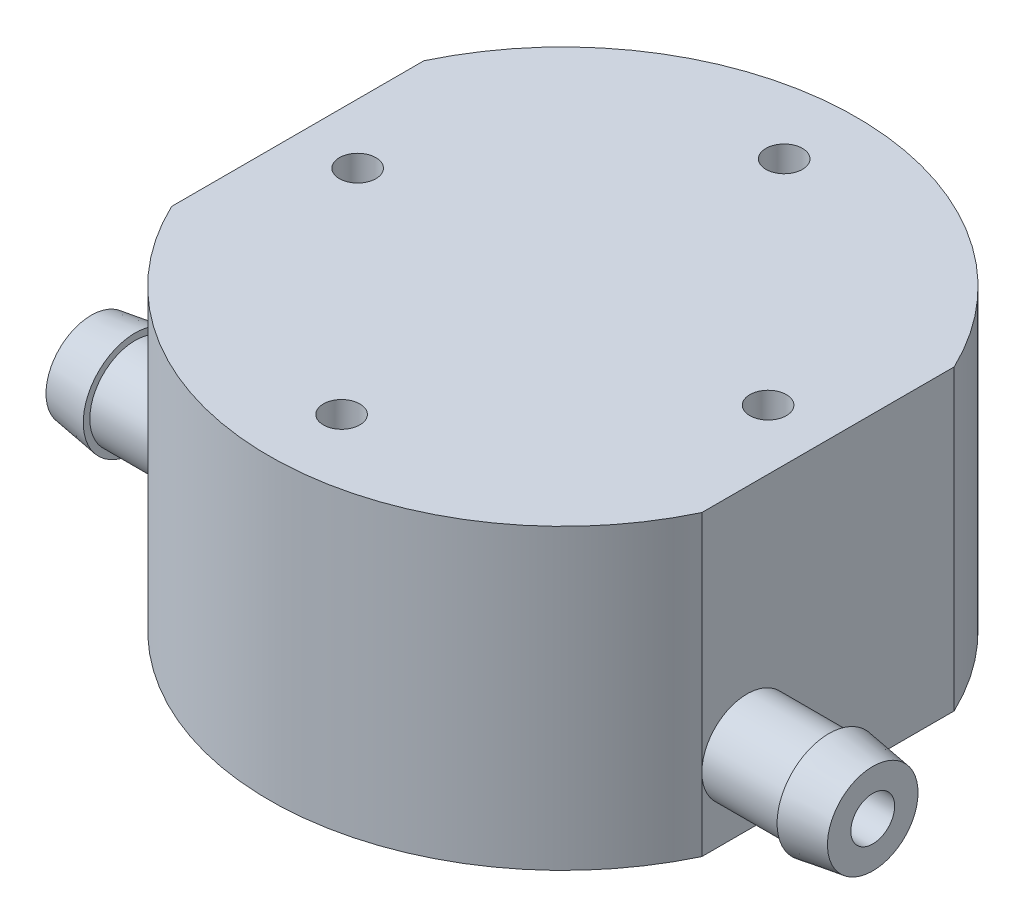
SolidWorks part; units mm, degrees
note: '?' marks a value the reader was unsure of.
ref_plane "Front Plane" through (0, 0, 0) normal (0, 0, 1) x (1, 0, 0)
ref_plane "Top Plane" through (0, 0, 0) normal (0, 1, 0) x (1, 0, 0)
ref_plane "Right Plane" through (0, 0, 0) normal (1, 0, 0) x (0, 0, -1)
sketch "Sketch1" plane through (0, 0, 0) normal (0, 1, 0) x (1, 0, 0)
  line L2 (-18.15, -8.6364) -> (-18.15, 8.6364)
  line L4 (18.15, -8.6364) -> (18.15, 8.6364)
  line L5 (-18.15, -8.6364) -> (18.15, 8.6364) construction
  line L6 (-18.15, 8.6364) -> (18.15, -8.6364) construction
  arc A0 (-18.15, -8.6364) -> (18.15, -8.6364) centre (0, 0) ccw
  arc A1 (18.15, 8.6364) -> (-18.15, 8.6364) centre (0, 0) ccw
  dimension "D1" = 40.2
  dimension "D2" = 36.3
extrude "Boss-Extrude1" add sketch "Sketch1" against normal blind 20.4
hole_wizard "M3x0.5 Tapped Hole1" positions "Sketch3" profile "Sketch4" tap size "M3x0.5" standard "ANSI Metric"
sketch "Sketch3" plane through (0, 0, 0) normal (0, 1, 0) x (1, 0, 0)
  line L0 (0, 20.1) -> (0, -20.1) construction
  line L3 (-18.15, 0) -> (18.15, 0) construction
  line L5 (-18.15, 8.6364) -> (-18.15, -8.6364) construction
  line L6 (18.15, -8.6364) -> (18.15, 8.6364) construction
  arc A0 (18.15, 8.6364) -> (-18.15, 8.6364) centre (0, 0) ccw construction
  arc A1 (-18.15, -8.6364) -> (18.15, -8.6364) centre (0, 0) ccw construction
  point P0 (0, 15.15)
  point P2 (0, -15.15)
  point P4 (14.05, 0)
  point P6 (-14.05, 0)
  dimension "D1" = 30.3
  dimension "D2" = 28.1
sketch "Sketch4" plane through (0, 0, -15.15) normal (1, 0, 0) x (0, 0, 1)
  line L0 (0, 0) -> (0, 8.2511)
  line L1 (0, 8.2511) -> (1.25, 7.5)
  line L2 (1.25, 7.5) -> (1.25, 0)
  line L5 (1.25, 0) -> (0, 0)
  line L10 (0, 8.2511) -> (-1.25, 7.5) construction
  line L11 (0, -6.35) -> (0, 107.95) construction
  dimension "Tap Drill Dia." = 2.5
  dimension "Tap Drill Depth" = 7.5
  dimension "Drill Angle" = 118
cosmetic thread "Hole Thread1" parameters "D1"=6, "D2"=3
cosmetic thread "Hole Thread2" parameters "D1"=6, "D2"=3
cosmetic thread "Hole Thread3" parameters "D1"=6, "D2"=3
cosmetic thread "Hole Thread4" parameters "D1"=6, "D2"=3
ref_plane "Plane1" through (0, 0, 20.1) normal (0, 0, 1) x (1, 0, 0)
ref_axis "Axis1" through (-18.15, 0, 20.1) along (1, 0, 0)?
sketch "Sketch5" plane through (18.15, 0, 0) normal (1, 0, 0) x (0, 0, -1)
  line L0 (-8.6364, -20.4) -> (-8.6364, 0) construction
  line L1 (-8.6364, -20.4) -> (8.6364, -20.4) construction
  circle A0 centre (-5.5364, -15.4) radius 3.1
  dimension "D1" = 6.2
  dimension "D2" = 5
extrude "Boss-Extrude3" add sketch "Sketch5" along direction (1, 0, 0) on the side of the normal offset from surface 8.6 and the other way offset from surface (44.9 mm away) 8.6
ref_point "Point1"
ref_plane "Nipple plane" through (0, 0, 5.5364) normal (0, 0, 1) x (1, 0, 0)
sketch "Sketch7" plane through (0, 0, 5.5364) normal (0, 0, 1) x (1, 0, 0)
  line L0 (26.75, -12.3) -> (23.75, -11.85)
  line L1 (23.75, -11.85) -> (23.75, -12.3)
  line L2 (26.75, -12.3) -> (18.15, -12.3) construction
  line L3 (26.75, -15.4) -> (18.15, -15.4) construction
  line L4 (26.75, -18.5) -> (26.75, -12.3) construction
  line L5 (18.15, -18.5) -> (18.15, -12.3) construction
  line L6 (23.75, -12.3) -> (26.75, -12.3)
  line L7 (-26.75, -12.3) -> (-23.75, -11.85)
  line L8 (-23.75, -11.85) -> (-23.75, -12.3)
  line L9 (-18.15, -12.3) -> (-26.75, -12.3) construction
  line L10 (-23.75, -12.3) -> (-26.75, -12.3)
  line L11 (-26.75, -12.3) -> (-26.75, -18.5) construction
  dimension "D1" = 3.55
  dimension "D2" = 3
  dimension "D3" = 3
revolve "Revolve1" add sketch "Sketch7" angle 360 about L3
sketch "Sketch8" plane through (26.75, 0, 0) normal (1, 0, 0) x (0, 0, -1)
  circle A0 centre (-5.5364, -15.4) radius 1.5
  circle A1 centre (-5.5364, -15.4) radius 3.1 construction
  dimension "D1" = 3
extrude "Cut-Extrude1" cut sketch "Sketch8" against normal through all
